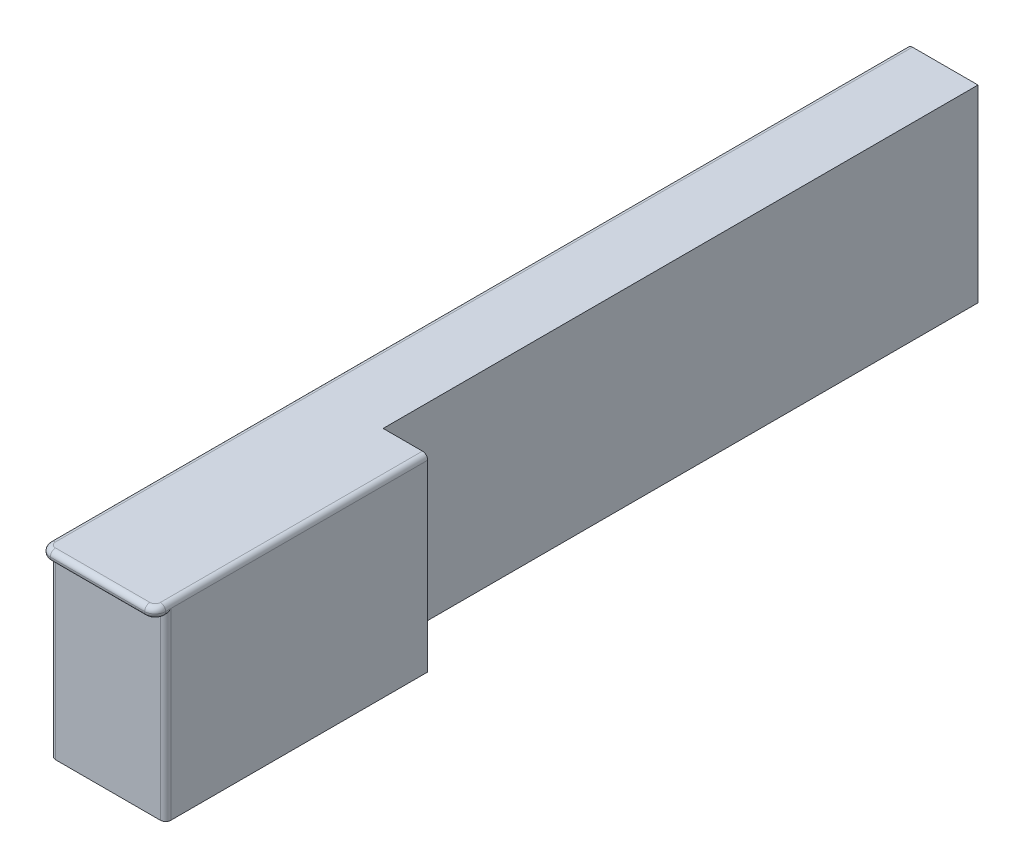
SolidWorks part; units mm, degrees
ref_plane "Front Plane" through (0, 0, 0) normal (0, 0, 1) x (1, 0, 0)
ref_plane "Top Plane" through (0, 0, 0) normal (0, 1, 0) x (1, 0, 0)
ref_plane "Right Plane" through (0, 0, 0) normal (1, 0, 0) x (0, 0, -1)
sketch "Sketch1" plane through (0, 0, 0) normal (0, 1, 0) x (1, 0, 0)
  line L1 (-11, -81.75) -> (11, -81.75)
  line L2 (-11, -81.75) -> (-11, 81.75)
  line L3 (-11, 81.75) -> (11, 81.75)
  line L4 (11, -81.75) -> (11, 81.75)
  line L5 (-11, -81.75) -> (11, 81.75) construction
  line L6 (-11, 81.75) -> (11, -81.75) construction
  point P0 (0, 0)
  dimension "D1" = 163.5
  dimension "D2" = 22
extrude "Boss-Extrude1" add sketch "Sketch1" along normal blind 36 contours L2 L3 L4 L1
fillet "Fillet1" radius 1 2 edges at (-11, 18, 81.75) (11, 18, 81.75)
sketch "Sketch2" plane through (0, 36, 0) normal (0, 1, 0) x (1, 0, 0)
  line L0 (11, -80.75) -> (11, 81.75) construction
  line L1 (-11, 81.75) -> (11, 81.75)
  line L2 (-11, 81.75) -> (-11, -83.75)
  line L3 (-11, -83.75) -> (11, -83.75)
  line L4 (11, 81.75) -> (11, -83.75)
  line L5 (-10, -81.75) -> (10, -81.75) construction
  dimension "D1" = 2
extrude "Boss-Extrude2" add sketch "Sketch2" against normal blind 2
fillet "Fillet2" radius 2 2 edges at (-11, 35, 83.75) (11, 35, 83.75)
fillet "Fillet3" radius 1 10 edges at (-11, 34, 81.25) (-10.4142, 34, 83.1642) (11, 34, 81.25) (10.4142, 34, 83.1642) (11, 36, 0) (10.4142, 36, 83.1642) (0, 36, 83.75) (-10.4142, 36, 83.1642) (-11, 36, 0) (0, 34, 83.75)
sketch "Sketch3" plane through (0, 36, 0) normal (0, 1, 0) x (1, 0, 0)
  line L1 (7.5, -31.75) -> (11, -31.75)
  line L2 (7.5, -31.75) -> (7.5, 81.75)
  line L3 (7.5, 81.75) -> (11, 81.75)
  line L4 (11, -31.75) -> (11, 81.75)
  line L5 (7.5, -31.75) -> (11, 81.75) construction
  line L6 (7.5, 81.75) -> (11, -31.75) construction
  line L7 (-10, -81.75) -> (10, -81.75) construction
  line L8 (-11, 81.75) -> (11, 81.75) construction
  line L9 (11, 81.75) -> (11, -80.75) construction
  dimension "D1" = 3.5
  dimension "D2" = 50
extrude "Cut-Extrude2" [suppressed] cut sketch "Sketch3" against normal through all
sketch "Sketch5" plane through (-11, 0, 0) normal (-1, 0, 0) x (0, 0, 1)
  line L0 (81.75, 34) -> (81.75, 0) construction
  line L1 (80.75, 0) -> (-81.75, 0) construction
  line L2 (-81.75, 36) -> (81.75, 36) construction
  line L3 (-81.75, 35) -> (-81.75, 0) construction
  line L8 (31.75, 36) -> (-81.75, 36)
  line L9 (31.75, 0) -> (31.75, 36)
  line L10 (-81.75, 0) -> (31.75, 0)
  line L11 (-81.75, 36) -> (-81.75, 0)
  dimension "D1" = 50
extrude "Cut-Extrude4" [suppressed] cut sketch "Sketch5" against normal blind 3.5
sketch "Sketch4" [suppressed] plane through (7.5, 0, 0) normal (1, 0, 0) x (0, 0, -1)
  line L4 (81.75, 36) -> (-31.75, 36)
  line L5 (-31.75, 36) -> (-31.75, 0)
  line L6 (-31.75, 0) -> (81.75, 0)
  line L7 (81.75, 0) -> (81.75, 36)
  line L8 (81.75, 36) -> (-31.75, 36)
  line L9 (-31.75, 36) -> (-31.75, 0)
  line L10 (-31.75, 0) -> (81.75, 0)
  line L11 (81.75, 0) -> (81.75, 36)
  dimension "D1" = 0
extrude "Cut-Extrude3" [suppressed] cut sketch "Sketch4" against normal blind 3.25
sketch "Sketch6" [suppressed] plane through (-7.5, 0, 0) normal (-1, 0, 0) x (0, 0, 1)
  line L4 (-81.75, 36) -> (-81.75, 0)
  line L5 (-81.75, 0) -> (31.75, 0)
  line L6 (31.75, 0) -> (31.75, 36)
  line L7 (31.75, 36) -> (-81.75, 36)
  line L8 (-81.75, 36) -> (-81.75, 0)
  line L9 (-81.75, 0) -> (31.75, 0)
  line L10 (31.75, 0) -> (31.75, 36)
  line L11 (31.75, 36) -> (-81.75, 36)
  dimension "D1" = 0
extrude "Cut-Extrude5" [suppressed] cut sketch "Sketch6" against normal blind 3.25
sketch "White" plane through (0, 0, 0) normal (0, 1, 0) x (1, 0, 0)
  line L0 (12.5, -81.75) -> (34.5, -81.75)
  line L1 (-11, -81.75) -> (11, -81.75)
  line L2 (-11, -81.75) -> (-11, 81.75)
  line L3 (-11, 81.75) -> (11, 81.75)
  line L4 (11, -81.75) -> (11, 81.75)
  line L5 (12.5, -81.75) -> (12.5, 81.75)
  line L6 (12.5, 81.75) -> (34.5, 81.75)
  line L7 (34.5, -81.75) -> (34.5, 81.75)
  line L8 (36, -81.75) -> (58, -81.75)
  line L9 (36, -81.75) -> (36, 81.75)
  line L10 (36, 81.75) -> (58, 81.75)
  line L11 (58, -81.75) -> (58, 81.75)
  line L12 (59.5, -81.75) -> (81.5, -81.75)
  line L13 (59.5, -81.75) -> (59.5, 81.75)
  line L14 (59.5, 81.75) -> (81.5, 81.75)
  line L15 (81.5, -81.75) -> (81.5, 81.75)
  line L16 (83, -81.75) -> (105, -81.75)
  line L17 (83, -81.75) -> (83, 81.75)
  line L18 (83, 81.75) -> (105, 81.75)
  line L19 (105, -81.75) -> (105, 81.75)
  line L20 (106.5, -81.75) -> (128.5, -81.75)
  line L21 (106.5, -81.75) -> (106.5, 81.75)
  line L22 (106.5, 81.75) -> (128.5, 81.75)
  line L23 (128.5, -81.75) -> (128.5, 81.75)
  line L24 (130, -81.75) -> (152, -81.75)
  line L25 (130, -81.75) -> (130, 81.75)
  line L26 (130, 81.75) -> (152, 81.75)
  line L27 (152, -81.75) -> (152, 81.75)
  dimension "D1" = 7
sketch "Black" plane through (0, 0, 0) normal (0, 1, 0) x (1, 0, 0)
  line L0 (-11, 81.75) -> (11, 81.75) construction
  line L1 (16, -31.75) -> (4, -31.75)
  line L2 (16, -31.75) -> (16, 81.75)
  line L3 (16, 81.75) -> (4, 81.75)
  line L4 (4, -31.75) -> (4, 81.75)
  line L6 (31, -31.75) -> (43, -31.75)
  line L7 (31, -31.75) -> (31, 81.75)
  line L8 (31, 81.75) -> (43, 81.75)
  line L9 (43, -31.75) -> (43, 81.75)
  line L10 (12.5, -81.75) -> (34.5, -81.75) construction
  line L11 (16, -31.75) -> (31, -31.75) construction
  line L12 (36, 81.75) -> (58, 81.75) construction
  line L13 (106.5, 81.75) -> (128.5, 81.75) construction
  line L14 (111.75, 81.75) -> (99.75, 81.75)
  line L15 (111.75, 81.75) -> (111.75, -31.75)
  line L16 (111.75, -31.75) -> (99.75, -31.75)
  line L17 (99.75, 81.75) -> (99.75, -31.75)
  line L18 (83, 81.75) -> (105, 81.75) construction
  line L19 (126.75, 81.75) -> (138.75, 81.75)
  line L20 (126.75, 81.75) -> (126.75, -31.75)
  line L21 (126.75, -31.75) -> (138.75, -31.75)
  line L22 (138.75, 81.75) -> (138.75, -31.75)
  line L23 (84.75, 81.75) -> (72.75, 81.75)
  line L24 (84.75, 81.75) -> (84.75, -31.75)
  line L25 (84.75, -31.75) -> (72.75, -31.75)
  line L26 (72.75, 81.75) -> (72.75, -31.75)
  line L27 (105, -81.75) -> (106.5, -81.75) construction
  point P14 (23.5, -81.75)
  point P15 (23.5, -31.75)
  point P36 (105.75, -81.75)
  point P37 (105.75, -31.75)
  dimension "D1" = 50
  dimension "D2" = 12
  dimension "D3" = 12
  dimension "D4" = 15
  dimension "D5" = 15
  dimension "D6" = 15
sketch "Sketch11" plane through (0, 36, 0) normal (0, 1, 0) x (1, 0, 0)
  line L1 (11, 81.75) -> (2.5, 81.75)
  line L2 (11, 81.75) -> (11, -31.75)
  line L3 (11, -31.75) -> (2.5, -31.75)
  line L4 (2.5, 81.75) -> (2.5, -31.75)
  line L5 (16, -31.75) -> (4, -31.75) construction
  dimension "D1" = 8.5
extrude "C" cut sketch "Sketch11" against normal through all
sketch "Sketch12" plane through (0, 36, 0) normal (0, 1, 0) x (1, 0, 0)
  line L0 (31, -31.75) -> (43, -31.75) construction
  line L1 (-11, 81.75) -> (-6, 81.75)
  line L2 (-11, 81.75) -> (-11, -31.75)
  line L3 (-11, -31.75) -> (-6, -31.75)
  line L4 (-6, 81.75) -> (-6, -31.75)
  line L5 (11, 81.75) -> (6, 81.75)
  line L6 (11, 81.75) -> (11, -31.75)
  line L7 (11, -31.75) -> (6, -31.75)
  line L8 (6, 81.75) -> (6, -31.75)
  dimension "D1" = 5
  dimension "D2" = 5
extrude "D" [suppressed] cut sketch "Sketch12" against normal through all
sketch "Sketch13" plane through (0, 36, 0) normal (0, 1, 0) x (1, 0, 0)
  line L1 (-11, 81.75) -> (-2.5, 81.75)
  line L2 (-11, 81.75) -> (-11, -31.75)
  line L3 (-11, -31.75) -> (-2.5, -31.75)
  line L4 (-2.5, 81.75) -> (-2.5, -31.75)
  line L5 (16, -31.75) -> (4, -31.75) construction
  dimension "D1" = 8.5
extrude "E" [suppressed] cut sketch "Sketch13" against normal through all
sketch "Sketch14" plane through (0, 36, 0) normal (0, 1, 0) x (1, 0, 0)
  line L0 (16, -31.75) -> (4, -31.75) construction
  line L1 (11, 81.75) -> (0.75, 81.75)
  line L2 (11, 81.75) -> (11, -31.75)
  line L3 (11, -31.75) -> (0.75, -31.75)
  line L4 (0.75, 81.75) -> (0.75, -31.75)
  dimension "D1" = 10.25
extrude "F" [suppressed] cut sketch "Sketch14" against normal through all
sketch "Sketch15" plane through (0, 36, 0) normal (0, 1, 0) x (1, 0, 0)
  line L1 (-11, 81.75) -> (-7.75, 81.75)
  line L2 (-11, 81.75) -> (-11, -31.75)
  line L3 (-11, -31.75) -> (-7.75, -31.75)
  line L4 (-7.75, 81.75) -> (-7.75, -31.75)
  line L5 (11, 81.75) -> (4.25, 81.75)
  line L6 (11, 81.75) -> (11, -31.75)
  line L7 (11, -31.75) -> (4.25, -31.75)
  line L8 (4.25, 81.75) -> (4.25, -31.75)
  line L9 (16, -31.75) -> (4, -31.75) construction
  dimension "D1" = 3.25
  dimension "D2" = 6.75
extrude "G" [suppressed] cut sketch "Sketch15" against normal through all
sketch "Sketch16" plane through (0, 36, 0) normal (0, 1, 0) x (1, 0, 0)
  line L0 (16, -31.75) -> (4, -31.75) construction
  line L1 (-11, 81.75) -> (-4.25, 81.75)
  line L2 (-11, 81.75) -> (-11, -31.75)
  line L3 (-11, -31.75) -> (-4.25, -31.75)
  line L4 (-4.25, 81.75) -> (-4.25, -31.75)
  line L5 (11, 81.75) -> (7.75, 81.75)
  line L6 (11, 81.75) -> (11, -31.75)
  line L7 (11, -31.75) -> (7.75, -31.75)
  line L8 (7.75, 81.75) -> (7.75, -31.75)
  dimension "D1" = 6.75
  dimension "D2" = 3.25
extrude "A" [suppressed] cut sketch "Sketch16" against normal through all
sketch "Sketch17" plane through (0, 36, 0) normal (0, 1, 0) x (1, 0, 0)
  line L0 (16, -31.75) -> (4, -31.75) construction
  line L1 (-11, 81.75) -> (-0.75, 81.75)
  line L2 (-11, 81.75) -> (-11, -31.75)
  line L3 (-11, -31.75) -> (-0.75, -31.75)
  line L4 (-0.75, 81.75) -> (-0.75, -31.75)
  dimension "D1" = 10.25
extrude "B" [suppressed] cut sketch "Sketch17" against normal through all
